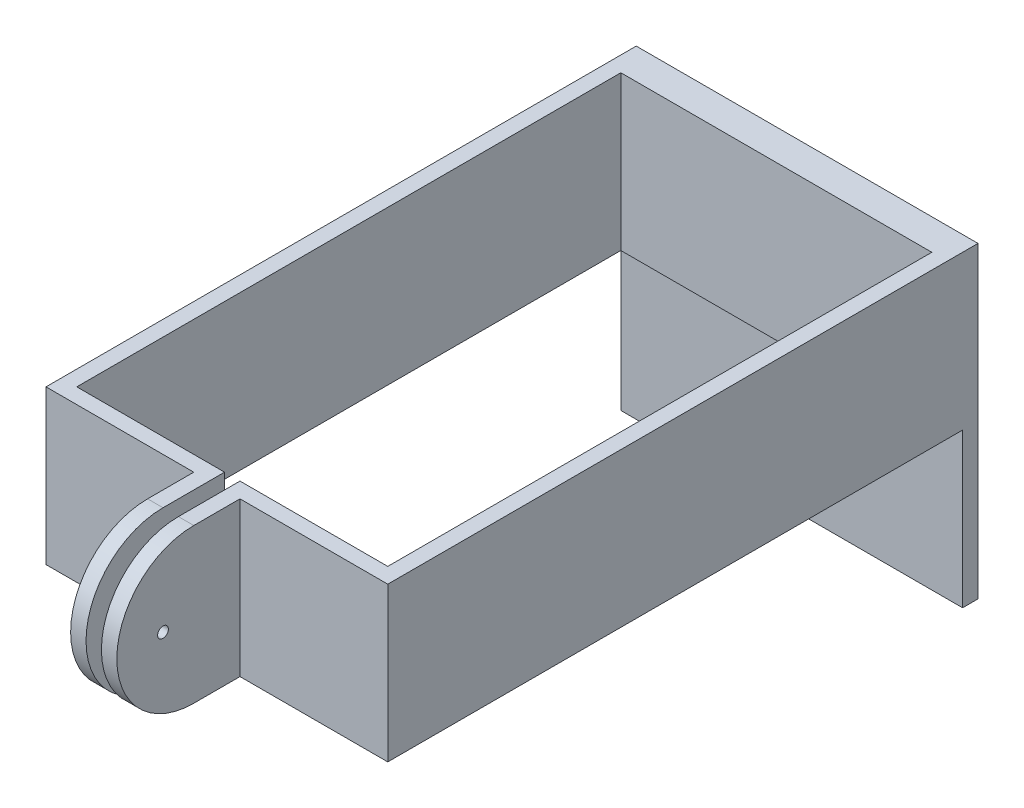
SolidWorks part; units mm, degrees
ref_plane "Front Plane" through (0, 0, 0) normal (0, 0, 1) x (1, 0, 0)
ref_plane "Top Plane" through (0, 0, 0) normal (0, 1, 0) x (1, 0, 0)
ref_plane "Right Plane" through (0, 0, 0) normal (1, 0, 0) x (0, 0, -1)
sketch "Sketch1" plane through (0, 0, 0) normal (0, 1, 0) x (1, 0, 0)
  line L0 (0, 0) -> (0, 176.7)
  line L1 (0, 176.7) -> (101, 176.7)
  line L2 (101, 176.7) -> (101, 0)
  line L3 (101, 0) -> (53, 0)
  line L4 (53, 0) -> (53, -5)
  line L5 (58, -5) -> (106, -5)
  line L6 (106, -5) -> (106, 181.7)
  line L7 (106, 181.7) -> (-5, 181.7)
  line L8 (-5, 181.7) -> (-5, -5)
  line L9 (-5, -5) -> (43, -5)
  line L10 (48, -5) -> (48, 0)
  line L11 (48, 0) -> (0, 0)
  line L12 (50.5, 175.8) -> (50.5, 86.5509) construction
  line L13 (48, 0) -> (50.5, 0) construction
  line L14 (50.5, 0) -> (53, 0) construction
  line L15 (48, -5) -> (48, -45)
  line L16 (48, -45) -> (43, -45)
  line L17 (43, -45) -> (43, -5)
  line L18 (53, -5) -> (53, -45)
  line L19 (53, -45) -> (58, -45)
  line L20 (58, -45) -> (58, -5)
  point P14 (50.5, 176.7)
  dimension "D1" = 176.7
  dimension "D2" = 101
  dimension "D3" = 5
  dimension "D4" = 5
  dimension "D5" = 5
  dimension "D6" = 5
  dimension "D7" = 5
  dimension "D8" = 5
  dimension "D9" = 40
extrude "Boss-Extrude1" add sketch "Sketch1" along normal blind 50
fillet "Fillet1" 2 edges at (45.5, 0, 45) (45.5, 50, 45) type full round first side face at (50.5, 0, -32.3) second side face at (50.5, 50, -32.3) middle face at (45.5, 25, 45)
fillet "Fillet2" 2 edges at (55.5, 0, 45) (55.5, 50, 45) type full round first side face at (50.5, 0, -35.425) second side face at (50.5, 50, -35.425) middle face at (55.5, 25, 45)
sketch "Sketch2" plane through (0, 0, -181.7) normal (0, 0, -1) x (-1, 0, 0)
  line L0 (5, 50) -> (5, 0) construction
  line L1 (-106, 50) -> (5, 50)
  line L2 (-106, 50) -> (-106, -50)
  line L3 (-106, -50) -> (5, -50)
  line L4 (5, 50) -> (5, -50)
  dimension "D1" = 100
extrude "Boss-Extrude2" add sketch "Sketch2" along normal blind 5
sketch "Sketch3" plane through (43, 0, 0) normal (-1, 0, 0) x (0, 0, 1)
  line L0 (5, 25) -> (35.3707, 25) construction
  line L1 (5, 50) -> (5, 0) construction
  line L2 (5, 50) -> (5, 0) construction
  circle A0 centre (30, 25) radius 1.75
  point P6 (30.236, 25)
  point P9 (30, 25)
  dimension "D1" = 3.5
  dimension "D2" = 25
extrude "Cut-Extrude1" cut sketch "Sketch3" against normal through all
sketch "Sketch4" plane through (0, 0, -181.7) normal (0, 0, 1) x (1, 0, 0)
  line L0 (50.5, -50) -> (50.5, -4.9507) construction
  line L1 (106, -50) -> (-5, -50) construction
  circle A0 centre (50.5, -30) radius 5
  point P6 (0, 0)
  point P7 (50, -23.0801)
  dimension "D1" = 20
  dimension "D2" = 10
extrude "Cut-Extrude2" cut sketch "Sketch4" against normal through all
ref_plane "Plane1" through (0, 25, 0) normal (0, 1, 0) x (1, 0, 0)
